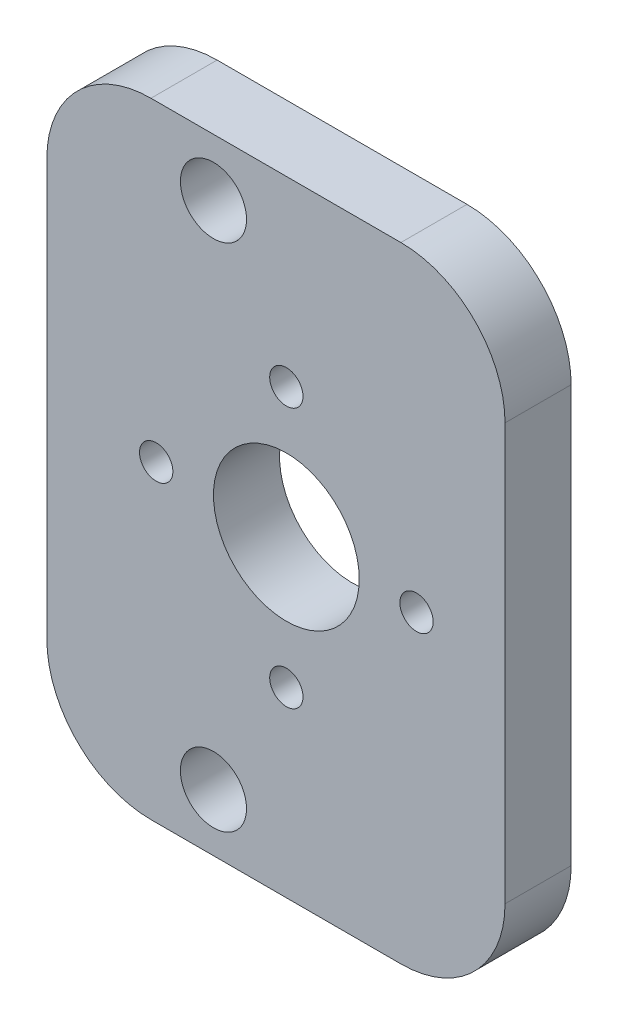
SolidWorks part; units mm, degrees
material "6061-T6 (SS)"
ref_plane "Front Plane" through (0, 0, 0) normal (0, 0, 1) x (1, 0, 0)
ref_plane "Top Plane" through (0, 0, 0) normal (0, 1, 0) x (1, 0, 0)
ref_plane "Right Plane" through (0, 0, 0) normal (1, 0, 0) x (0, 0, -1)
sketch "Sketch2" plane through (0, 0, 0) normal (0, 0, 1) x (1, 0, 0)
  line L0 (0, 0) -> (21, 0) construction
  line L1 (-23, -30) -> (21, -30)
  line L2 (-23, -30) -> (-23, 30)
  line L3 (-23, 30) -> (21, 30)
  line L4 (21, -30) -> (21, 30)
  line L5 (-23, -30) -> (21, 30) construction
  line L6 (-23, 30) -> (21, -30) construction
  circle A0 centre (0, 0) radius 7
  circle A1 centre (-7, 24.5) radius 3.175
  circle A2 centre (-7, -24.5) radius 3.175
  point P3 (-1, 0)
  point P8 (0, 12.5)
  point P12 (12.5, 0)
  point P13 (0, -12.5)
  point P14 (-12.5, 0)
  point P15 (0, 0)
  dimension "D1" = 14
  dimension "D9" = 6.35
  dimension "D2" = 30
  dimension "D3" = 23
  dimension "D4" = 21
  dimension "D5" = 12.5
  dimension "D7" = 5.5
  dimension "D8" = 16
  dimension "D6" = 4
extrude "Boss-Extrude1" add sketch "Sketch2" along normal mid plane 6.35
hole_wizard "M3 Clearance Hole1" positions "Sketch3" profile "Sketch4" hole size "M3" standard "ANSI Metric" end condition through all
sketch "Sketch3" plane through (0, 0, 3.175) normal (0, 0, 1) x (1, 0, 0)
  point P0 (0, 12.5)
  point P3 (12.5, 0)
  point P6 (0, -12.5)
  point P9 (-12.5, 0)
sketch "Sketch4" plane through (0, 12.5, 3.175) normal (1, 0, 0) x (0, -1, 0)
  line L0 (0, 0) -> (0, 6.35)
  line L1 (0, 6.35) -> (1.6, 6.35)
  line L2 (1.6, 6.35) -> (1.6, 0)
  line L5 (1.6, 0) -> (0, 0)
  line L11 (0, -6.35) -> (0, 107.95) construction
  dimension "Thru Hole Dia." = 3.2
  dimension "Thru Hole Depth" = 6.35
fillet "Fillet1" radius 10 4 edges at (21, -30, 0) (21, 30, 0) (-23, -30, 0) (-23, 30, 0)
equation "\"D9@Sketch2\"=0.25in"
